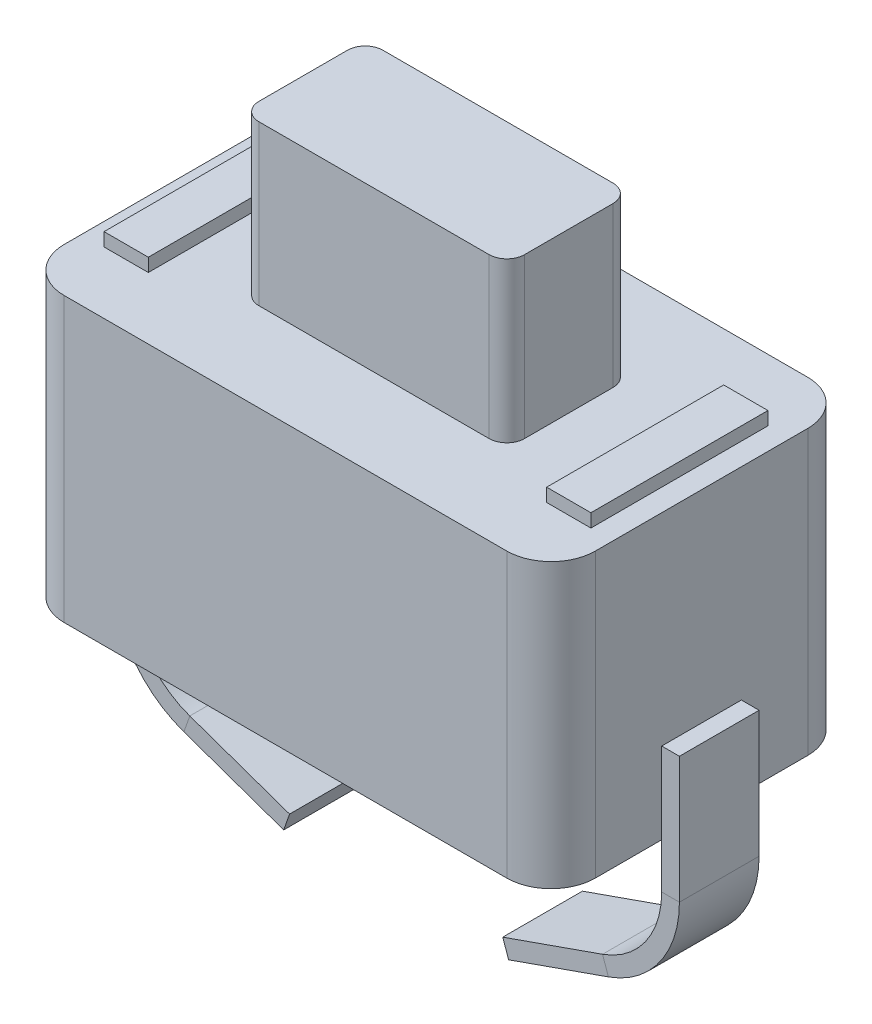
SolidWorks part; units mm, degrees
ref_plane "Front Plane" through (0, 0, 0) normal (0, 0, 1) x (1, 0, 0)
ref_plane "Top Plane" through (0, 0, 0) normal (0, 1, 0) x (1, 0, 0)
ref_plane "Right Plane" through (0, 0, 0) normal (1, 0, 0) x (0, 0, -1)
sketch "Sketch1" plane through (0, 0, 0) normal (0, 1, 0) x (1, 0, 0)
  line L1 (3, -1.7) -> (-3, -1.7)
  line L2 (3, -1.7) -> (3, 1.7)
  line L3 (3, 1.7) -> (-3, 1.7)
  line L4 (-3, -1.7) -> (-3, 1.7)
  line L5 (3, -1.7) -> (-3, 1.7) construction
  line L6 (3, 1.7) -> (-3, -1.7) construction
  point P0 (0, 0)
  dimension "D1" = 6
  dimension "D2" = 3.4
extrude "Boss-Extrude1" add sketch "Sketch1" along normal blind 3.2
sketch "Sketch2" plane through (0, 3.2, 0) normal (0, 1, 0) x (1, 0, 0)
  line L0 (-3, 1.7) -> (-3, -1.7) construction
  line L1 (1.5, -0.7) -> (-1.5, -0.7)
  line L2 (1.5, -0.7) -> (1.5, 0.7)
  line L3 (1.5, 0.7) -> (-1.5, 0.7)
  line L4 (-1.5, -0.7) -> (-1.5, 0.7)
  line L5 (1.5, -0.7) -> (-1.5, 0.7) construction
  line L6 (1.5, 0.7) -> (-1.5, -0.7) construction
  line L7 (-2.25, -1) -> (-2.75, -1)
  line L8 (-2.25, -1) -> (-2.25, 1)
  line L9 (-2.25, 1) -> (-2.75, 1)
  line L10 (-2.75, -1) -> (-2.75, 1)
  line L11 (-2.25, -1) -> (-2.75, 1) construction
  line L12 (-2.25, 1) -> (-2.75, -1) construction
  line L13 (2.75, -1) -> (2.25, -1)
  line L14 (2.75, -1) -> (2.75, 1)
  line L15 (2.75, 1) -> (2.25, 1)
  line L16 (2.25, -1) -> (2.25, 1)
  line L17 (2.75, -1) -> (2.25, 1) construction
  line L18 (2.75, 1) -> (2.25, -1) construction
  line L19 (3, -1.7) -> (3, 1.7) construction
  point P0 (0, 0)
  point P6 (-2.5, 0)
  point P11 (2.5, 0)
  dimension "D1" = 3
  dimension "D2" = 1.4
  dimension "D3" = 2
  dimension "D4" = 0.5
  dimension "D5" = 0.5
  dimension "D6" = 0.5
extrude "Boss-Extrude2" add sketch "Sketch2" along normal blind 1.8 contours L4 L1 L2 L3 region at (0, 3.2, 0)
extrude "Boss-Extrude3" add sketch "Sketch2<3>" along normal blind 0.15 contours L10 L7 L8 L9 | L16 L13 L14 L15 region at (-2.5, 3.2, 0) region at (2.5, 3.2, 0)
sketch "Sketch2<3>" plane through (0, 3.2, 0) normal (0, 1, 0) x (1, 0, 0) same geometry as "Sketch2"
fillet "Fillet1" radius 0.2 4 edges at (-1.5, 4.1, -0.7) (1.5, 4.1, -0.7) (1.5, 4.1, 0.7) (-1.5, 4.1, 0.7)
sketch "Sketch3" plane through (0, 0, 0) normal (0, -1, 0) x (1, 0, 0)
  line L0 (-3, -1.7) -> (-3, 1.7) construction
  line L1 (-3, -0.45) -> (-3.2, -0.45)
  line L2 (-3, -0.45) -> (-3, 0.45)
  line L3 (-3, 0.45) -> (-3.2, 0.45)
  line L4 (-3.2, -0.45) -> (-3.2, 0.45)
  point P12 (-3.2, 0)
  dimension "D1" = 0.9
  dimension "D2" = 0.2
fillet "Fillet3" radius 0.5 4 edges at (3, 1.6, 1.7) (3, 1.6, -1.7) (-3, 1.6, -1.7) (-3, 1.6, 1.7)
sketch "Sketch4" plane through (0, 0, 0) normal (0, 0, 1) x (1, 0, 0)
  line L0 (-3, 0) -> (-3, -0.5107)
  line L1 (-2.3315, -1.4541) -> (-1.2041, -1.8502)
  line L2 (-3, 0) -> (-3, 0.9173)
  line L3 (-3, 0) -> (-3, 3.2) construction
  arc A0 (-3, -0.5107) -> (-2.3315, -1.4541) centre (-2, -0.5107) ccw
  point P6 (-1.4858, -2.144)
  point P10 (-1, -0.5107)
  point P11 (-1.2727, -2.5168)
  point P12 (-1.7271, -1.9885)
  point P13 (-1.2041, -1.8502)
  dimension "D1" = 1
sweep "Sweep1" add profiles "Sketch3" path "Sketch4"
mirror "Mirror1" about plane through (0, 0, 0) normal (1, 0, 0) of "Sweep1"
equation "\"D6@Sketch2\"=\"D5@Sketch2\""
